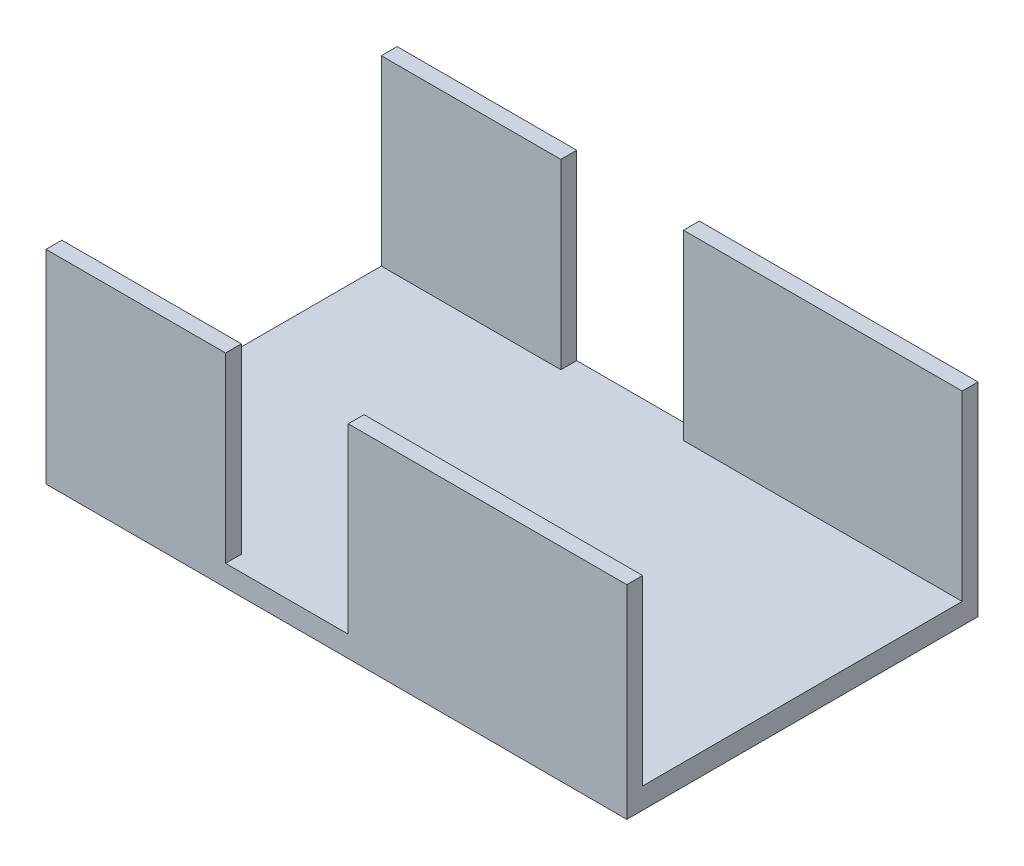
SolidWorks part; units mm, degrees
ref_plane "前视基准面" through (0, 0, 0) normal (0, 0, 1) x (1, 0, 0)
ref_plane "上视基准面" through (0, 0, 0) normal (0, 1, 0) x (1, 0, 0)
ref_plane "右视基准面" through (0, 0, 0) normal (1, 0, 0) x (0, 0, -1)
other "Configuration Table"
sketch "草图1" plane through (0, 0, 0) normal (0, 1, 0) x (1, 0, 0)
  line L0 (0, 3) -> (34, 3)
  line L1 (0, 0) -> (110, 0)
  line L2 (0, 0) -> (0, 66.5)
  line L3 (0, 66.5) -> (110, 66.5)
  line L4 (110, 0) -> (110, 66.5)
  line L5 (110, 63.5) -> (57.23, 63.5)
  line L6 (57.23, 66.5) -> (57.23, 63.5)
  line L7 (34, 66.5) -> (34, 63.5)
  line L8 (34, 3) -> (34, 0)
  line L9 (34, 63.5) -> (0, 63.5)
  line L10 (57.23, 3) -> (57.23, 0)
  line L11 (57.23, 3) -> (110, 3)
  dimension "D1" = 110
  dimension "D2" = 66.5
  dimension "D3" = 3
  dimension "D4" = 3
  dimension "D5" = 52.77
  dimension "D6" = 34
extrude "凸台-拉伸1" add sketch "草图1" along normal blind 4 contours L10 L11 L4 L5 L6 L3 L7 L9 L2 L0 L8 L1 region at (54.8075, 0, -33.25)
extrude "凸台-拉伸2" add sketch "草图1<3>" along normal blind 38.5 contours L3 L6 L5 L4 | L9 L7 L3 L2 | L8 L0 L2 L1 | L11 L10 L1 L4 region at (17, 0, -1.5) region at (17, 0, -65) region at (83.615, 0, -1.5) region at (83.615, 0, -65)
sketch "草图1<3>" plane through (0, 0, 0) normal (0, 1, 0) x (1, 0, 0) same geometry as "草图1"
